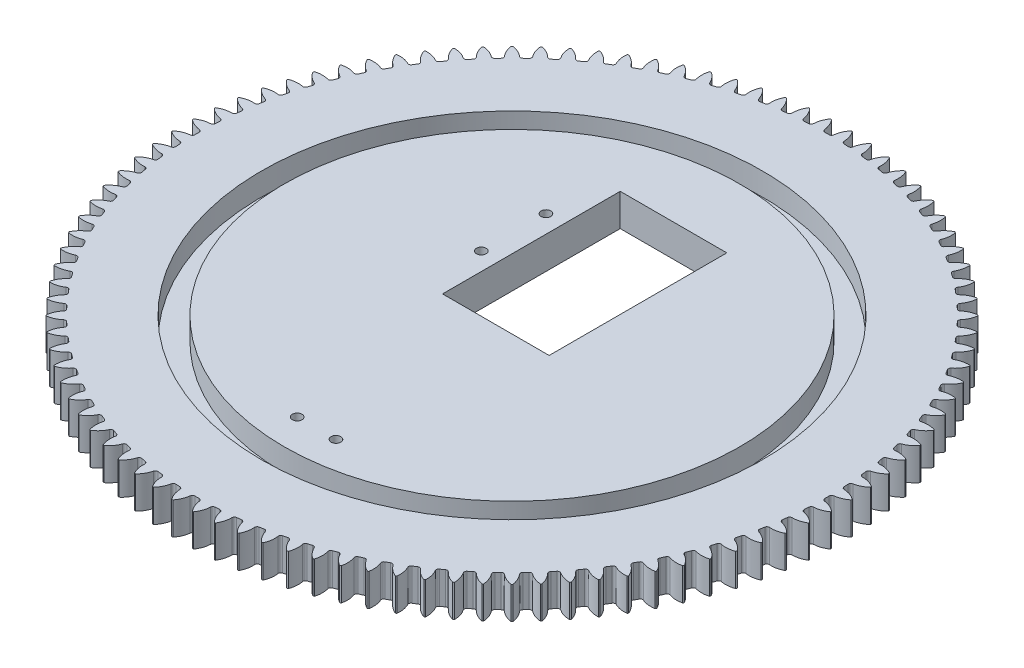
SolidWorks part; units mm, degrees
ref_plane "Front Plane" through (0, 0, 0) normal (0, 0, 1) x (1, 0, 0)
ref_plane "Top Plane" through (0, 0, 0) normal (0, 1, 0) x (1, 0, 0)
ref_plane "Right Plane" through (0, 0, 0) normal (1, 0, 0) x (0, 0, -1)
sketch "Sketch1" plane through (0, 0, 0) normal (0, 1, 0) x (1, 0, 0)
  circle A1 centre (0, 0) radius 102
  dimension "D2" = 204
extrude "Boss-Extrude1" add sketch "Sketch1" along normal blind 10
sketch "Sketch2" plane through (0, 10, 0) normal (0, 1, 0) x (1, 0, 0)
  line L0 (0, 0) -> (0, 102) construction
  line L1 (-1.3895, 97.4901) -> (0, 0) construction
  line L2 (0, 94.8463) -> (-2.5918, 101.9671) construction
  circle A0 centre (0, 0) radius 102 construction
  arc A1 (1.3895, 97.4901) -> (-1.3895, 97.4901) centre (0, 0) ccw
  arc A2 (1.8707, 99.9825) -> (-1.8707, 99.9825) centre (0, 0) ccw construction
  arc A3 (3.0148, 101.9554) -> (-3.0148, 101.9554) centre (0, 0) ccw
  arc A4 (-3.0148, 101.9554) -> (-1.3895, 97.4901) centre (-8.6195, 97.387) cw
  arc A5 (3.0148, 101.9554) -> (1.3895, 97.4901) centre (8.6195, 97.387) ccw
  point P2 (0, 0)
  point P5 (0, 0)
  point P16 (-1.8249, 99.8601)
  dimension "D1" = 204
  dimension "D2" = 200
  dimension "D3" = 4.5
  dimension "D4" = 20
  dimension "D5" = 3.7416
extrude "Cut-Extrude1" cut sketch "Sketch2" against normal through all
fillet "Fillet1" radius 0.76 2 edges at (1.3895, 5, -97.4901) (-1.3895, 5, -97.4901)
pattern_circular "CirPattern2" count 100 over 360 about axis through (0, 10, 0) along (0, 1, 0) of "Cut-Extrude1", "Fillet1"
sketch "Sketch3" plane through (0, 10, 0) normal (0, 1, 0) x (1, 0, 0)
  circle A0 centre (0, 0) radius 73 construction
  circle A1 centre (0, 0) radius 77.5
  circle A2 centre (0, 0) radius 70.5
  point P5 (0, 0)
  point P6 (0, 0)
  dimension "D1" = 146
  dimension "D2" = 7
  dimension "D3" = 4.5
extrude "Cut-Extrude2" cut sketch "Sketch3" against normal blind 7
sketch "Sketch4" plane through (0, 0, 0) normal (0, -1, 0) x (1, 0, 0)
  circle A0 centre (0, 0) radius 100 construction
  point P3 (0, 0)
  dimension "D1" = 200
sketch "Sketch6" plane through (0, 0, 0) normal (0, -1, 0) x (1, 0, 0)
  line L1 (-16.5, -50) -> (16.5, -50)
  line L2 (-16.5, -50) -> (-16.5, 5)
  line L3 (-16.5, 5) -> (16.5, 5)
  line L4 (16.5, -50) -> (16.5, 5)
  point P4 (0, 5)
  dimension "D1" = 33
  dimension "D2" = 55
  dimension "D3" = 5
extrude "Cut-Extrude3" cut sketch "Sketch6" against normal through all
ref_plane "Plane1" through (21.5, 0, 0) normal (1, 0, 0) x (0, 0, -1)
sketch "Sketch7" plane through (21.5, 0, 0) normal (1, 0, 0) x (0, 0, -1)
  line L1 (1.5, 0) -> (43.5, 0)
  line L2 (1.5, 0) -> (1.5, -47)
  line L3 (1.5, -47) -> (43.5, -47)
  line L4 (43.5, 0) -> (43.5, -47)
  line L5 (50, 10) -> (-5, 10) construction
  circle A0 centre (22.5, -26) radius 11.5
  circle A1 centre (7, -10.5) radius 1.5
  circle A2 centre (38, -10.5) radius 1.5
  circle A3 centre (38, -41.5) radius 1.5
  circle A4 centre (7, -41.5) radius 1.5
  point P5 (22.5, 0)
  point P17 (27.3757, -21)
  point P18 (22.5, -47)
  point P21 (22.5, 10)
  point P22 (0, 0)
  point P23 (0, 0)
  dimension "D4" = 23
  dimension "D9" = 3
  dimension "D1" = 42
  dimension "D2" = 21
  dimension "D3" = 47
  dimension "D5" = 5.5
  dimension "D6" = 10.5
  dimension "D7" = 5.5
  dimension "D8" = 5.5
extrude "Boss-Extrude2" add sketch "Sketch7" along normal blind 5
sketch "Sketch9" plane through (0, 0, 0) normal (0, -1, 0) x (1, 0, 0)
  line L1 (26.5, -1.5) -> (68.5, -1.5)
  line L2 (26.5, -1.5) -> (26.5, -43.5)
  line L3 (26.5, -43.5) -> (68.5, -43.5)
  line L4 (68.5, -1.5) -> (68.5, -43.5)
  point P5 (0, 0)
  point P6 (0, 0)
  point P8 (0, 0)
  dimension "D1" = 42
extrude "Boss-Extrude3" add sketch "Sketch9" along normal blind 5
sketch "Sketch10" plane through (0, 0, 0) normal (0, -1, 0) x (1, 0, 0)
  line L0 (-6, 60.5) -> (6, 60.5) construction
  line L1 (68.5, -1.5) -> (21.5, -1.5) construction
  circle A0 centre (-6, 60.5) radius 1.5
  circle A1 centre (6, 60.5) radius 1.5
  point P2 (0, 60.5)
  dimension "D2" = 3
  dimension "D1" = 62
  dimension "D3" = 12
extrude "Cut-Extrude4" cut sketch "Sketch10" against normal through all
sketch "Sketch11" plane through (0, 0, 0) normal (0, -1, 0) x (1, 0, 0)
  line L0 (-16.5, 5) -> (-16.5, -50) construction
  line L1 (-16.5, -22.5) -> (16.5, -22.5) construction
  line L2 (16.5, -50) -> (16.5, 5) construction
  circle A0 centre (-22, -12.5) radius 1.5
  circle A1 centre (-22, -32.5) radius 1.5
  point P4 (-16.5, -22.5)
  dimension "D2" = 3
  dimension "D1" = 5.5
  dimension "D3" = 10
extrude "Cut-Extrude5" cut sketch "Sketch11" against normal through all
equation "\"Module\"= 2"
equation "\"No. of Teeth\"= 100"
equation "\"Bore Diameter\" =2"
equation "\"Pressure Angle\"= 20deg"
equation "\"Outer Diameter\"= ( \"No. of Teeth\" + 2 ) * \"Module\""
equation "\"Pitch Diameter\"= \"No. of Teeth\" * \"Module\""
equation "\"Backlash\"= 0.3 * \"Module\""
equation "\"Arc Length\"= ( \"Module\" * pi ) / 2 + \"Backlash\""
equation "\"Fillet Radius\"= .38 * \"Module\""
equation "\"Tooth Depth\"= IIF ( \"Module\" <= 1.25 , 2.4 * \"Module\" , 2.25 * \"Module\" )"
equation "\"D2@Sketch1\"=\"Outer Diameter\""
equation "\"D2@Sketch2\"=\"Pitch Diameter\""
equation "\"D1@Sketch2\"=\"Outer Diameter\""
equation "\"D3@Sketch2\"=\"Tooth Depth\""
equation "\"D4@Sketch2\"=\"Pressure Angle\""
equation "\"D5@Sketch2\"=\"Arc Length\""
equation "\"D1@Fillet1\"=\"Fillet Radius\""
equation "\"D1@CirPattern2\"=\"No. of Teeth\""
equation "\"D1@Sketch4\"=\"Pitch Diameter\""
